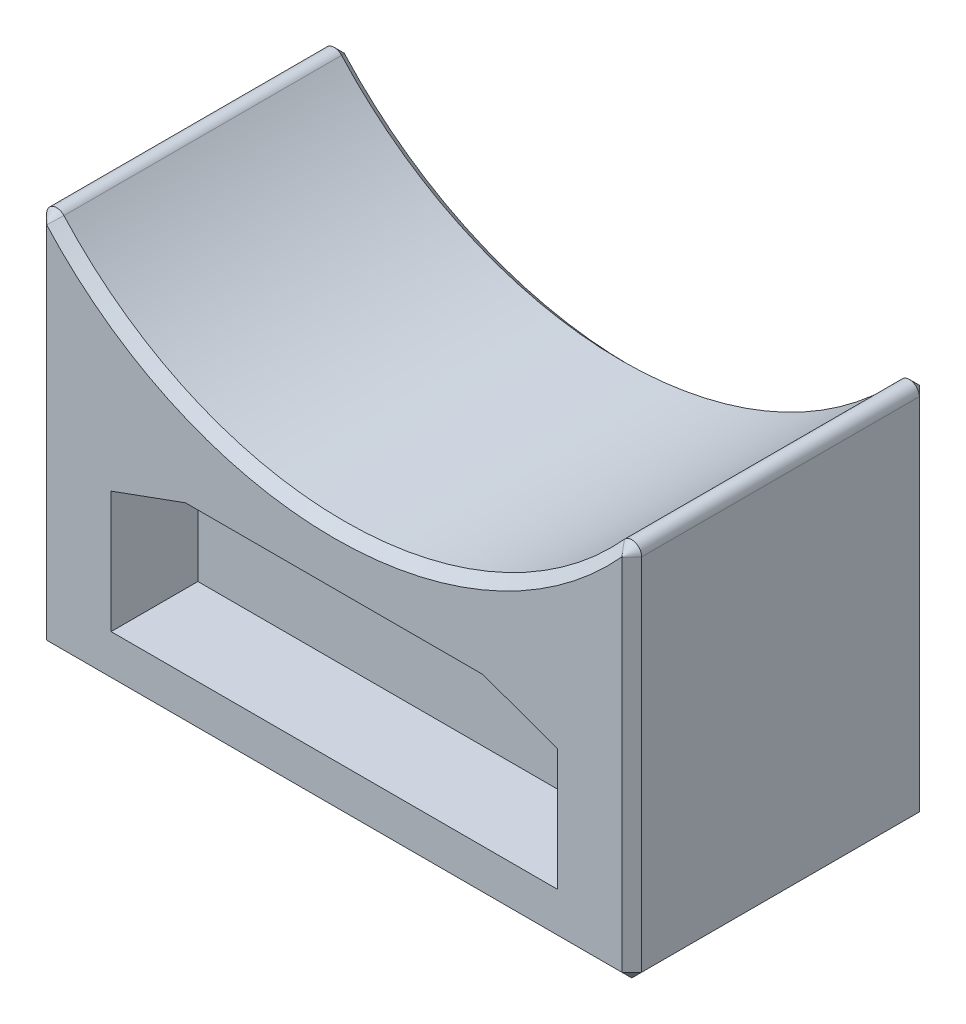
SolidWorks part; units mm, degrees
ref_plane "Front Plane" through (0, 0, 0) normal (0, 0, 1) x (1, 0, 0)
ref_plane "Top Plane" through (0, 0, 0) normal (0, 1, 0) x (1, 0, 0)
ref_plane "Right Plane" through (0, 0, 0) normal (1, 0, 0) x (0, 0, -1)
sketch "Sketch1" plane through (0, 0, 0) normal (0, 0, 1) x (1, 0, 0)
  line L0 (-33.7139, -127) -> (49966.2861, -127) construction
  line L1 (0, -76.2) -> (0, -127)
  line L2 (0, -127) -> (60, -127)
  line L3 (60, -127) -> (60, -46.9728)
  circle A0 centre (0, 0) radius 76.2 construction
  arc A1 (60, -46.9728) -> (0, -76.2) centre (0, 0) cw
  point P5 (0, 0)
  point P8 (0, 0)
  dimension "D1" = 152.4
  dimension "D2" = 127
  dimension "D3" = 60
extrude "Boss-Extrude1" add sketch "Sketch1" along normal blind 60
mirror "Mirror1" about plane through (0, -76.2, 60) normal (1, 0, 0) of "Boss-Extrude1"
fillet "Fillet1" radius 2 2 edges at (60, -46.9728, 30) (-60, -46.9728, 30)
chamfer "Chamfer1" distance 2 angle 45 14 edges at (-60, -127, 30) (-58.7188, -50.5859, 0) (-60, -89.7261, 0) (0, -127, 0) (0, -76.2, 0) (58.7188, -50.5859, 0) (60, -89.7261, 0) (60, -127, 30) (0, -127, 60) (-60, -89.7261, 60) (-58.7188, -50.5859, 60) (0, -76.2, 60) (58.7188, -50.5859, 60) (60, -89.7261, 60)
sketch "Sketch2" plane through (0, 0, 0) normal (0, 0, -1) x (-1, 0, 0)
  line L0 (0, -127) -> (0, -76.2) construction
  line L1 (45, -117) -> (-45, -117)
  line L2 (45, -117) -> (45, -87)
  line L3 (45, -87) -> (-45, -87)
  line L4 (-45, -117) -> (-45, -87)
  line L5 (58, -127) -> (-58, -127) construction
  line L6 (-60, -125) -> (-60, -52.4523) construction
  arc A0 (-56.5166, -51.1108) -> (56.5166, -51.1108) centre (0, 0) ccw construction
  point P11 (0, -117)
  dimension "D1" = 30
  dimension "D2" = 15
  dimension "D3" = 10
extrude "Cut-Extrude1" cut sketch "Sketch2" against normal blind 17.5
chamfer "Chamfer2" distance 15 angle 20 3 edges at (-45, -87, 8.75) (0, -87, 17.5) (45, -87, 8.75) first distance on face at (0, -87, 8.75)
ref_plane "Plane1" through (0, 0, 30) normal (0, 0, -1) x (-1, 0, 0)
mirror "Mirror2" about plane through (0, 0, 30) normal (0, 0, -1) of "Chamfer2", "Cut-Extrude1"
